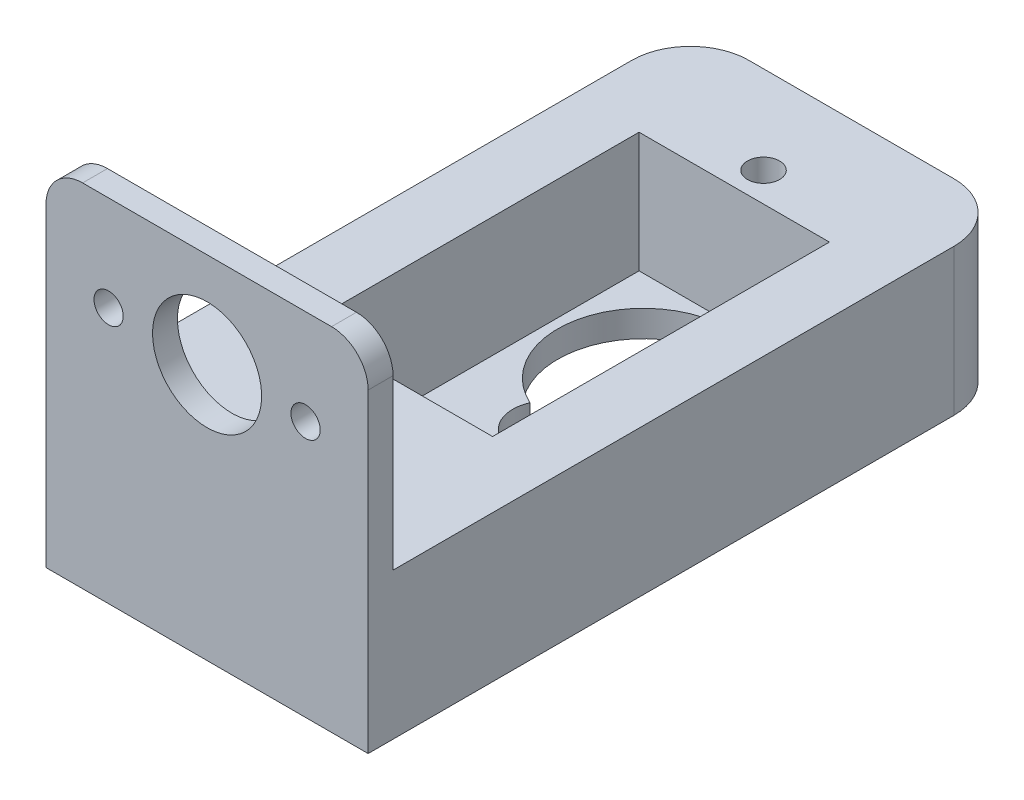
SolidWorks part; units mm, degrees
ref_plane "Front Plane" through (0, 0, 0) normal (0, 0, 1) x (1, 0, 0)
ref_plane "Top Plane" through (0, 0, 0) normal (0, 1, 0) x (1, 0, 0)
ref_plane "Right Plane" through (0, 0, 0) normal (1, 0, 0) x (0, 0, -1)
sketch "Sketch1" plane through (0, 0, 0) normal (0, 1, 0) x (1, 0, 0)
  line L1 (0, 0) -> (22, 0)
  line L2 (0, 0) -> (0, 44)
  line L3 (0, 44) -> (22, 44)
  line L4 (22, 0) -> (22, 44)
  dimension "D1" = 22
  dimension "D2" = 44
extrude "Boss-Extrude1" add sketch "Sketch1" along normal blind 10 contours L2 L3 L4 L1
sketch "Sketch2" plane through (0, 10, 0) normal (0, 1, 0) x (1, 0, 0)
  line L0 (0, 0) -> (0, 44) construction
  line L1 (4.5, 36) -> (17.5, 36)
  line L2 (4.5, 36) -> (4.5, 13)
  line L3 (4.5, 13) -> (17.5, 13)
  line L4 (17.5, 36) -> (17.5, 13)
  line L5 (0, 0) -> (22, 0) construction
  dimension "D1" = 13
  dimension "D2" = 23
  dimension "D3" = 4.5
  dimension "D4" = 13
extrude "Cut-Extrude1" cut sketch "Sketch2" against normal blind 8.2
sketch "Sketch3" plane through (0, 1.8, 0) normal (0, 1, 0) x (1, 0, 0)
  line L0 (17.5, 36) -> (4.5, 36) construction
  line L1 (17.5, 13) -> (17.5, 36) construction
  circle A0 centre (11, 29.8) radius 5.85
  dimension "D1" = 6.2
  dimension "D3" = 11.7
  dimension "D2" = 6.5
extrude "Cut-Extrude2" cut sketch "Sketch3" against normal through all
sketch "Sketch4" plane through (0, 10, 0) normal (0, 1, 0) x (1, 0, 0)
  line L0 (0, 0) -> (0, 44) construction
  line L1 (0, 1.7) -> (22, 1.7)
  line L2 (0, 1.7) -> (0, 0)
  line L3 (0, 0) -> (22, 0)
  line L4 (22, 1.7) -> (22, 0)
  dimension "D1" = 1.7
extrude "Boss-Extrude2" add sketch "Sketch4" along normal blind 14
sketch "Sketch5" plane through (0, 0, -1.7) normal (0, 0, -1) x (-1, 0, 0)
  line L0 (-22, 24) -> (-22, 10) construction
  line L1 (-22, 10) -> (0, 10) construction
  circle A0 centre (-11, 17.5) radius 3.725
  circle A3 centre (-17.725, 17.5) radius 1
  circle A4 centre (-4.275, 17.5) radius 1
  dimension "D1" = 7.45
  dimension "D2" = 3
  dimension "D5" = 7.5
  dimension "D3" = 3
  dimension "D4" = 11
extrude "Cut-Extrude3" cut sketch "Sketch5" against normal through all contours A0
extrude "Cut-Extrude4" cut sketch "Sketch5<3>" against normal blind 10
sketch "Sketch5<3>" plane through (0, 0, -1.7) normal (0, 0, -1) x (-1, 0, 0) same geometry as "Sketch5"
sketch "Sketch6" plane through (0, 10, 0) normal (0, 1, 0) x (1, 0, 0)
  line L0 (17.5, 36) -> (4.5, 36) construction
  line L1 (4.5, 13) -> (17.5, 13) construction
  circle A0 centre (11, 38) radius 1.1
  circle A1 centre (11, 10) radius 1.1
  dimension "D1" = 2
  dimension "D2" = 2.2
  dimension "D4" = 2.2
  dimension "D3" = 3
extrude "Cut-Extrude5" cut sketch "Sketch6" against normal blind 4
fillet "Fillet1" radius 4 2 edges at (0, 5, -44) (22, 5, -44)
fillet "Fillet2" radius 2.5 2 edges at (0, 24, -0.85) (22, 24, -0.85)
sketch "Sketch7" plane through (0, 1.8, 0) normal (0, 1, 0) x (1, 0, 0)
  arc A0 (8.5739, 24.4768) -> (12.9671, 24.4768) centre (10.7705, 23.5098) ccw
  circle A1 centre (11, 29.8) radius 5.85 construction
  arc A2 (8.5739, 24.4768) -> (12.9671, 24.4768) centre (10.7705, 29.8856) ccw
extrude "Cut-Extrude6" cut sketch "Sketch7" against normal blind 10
